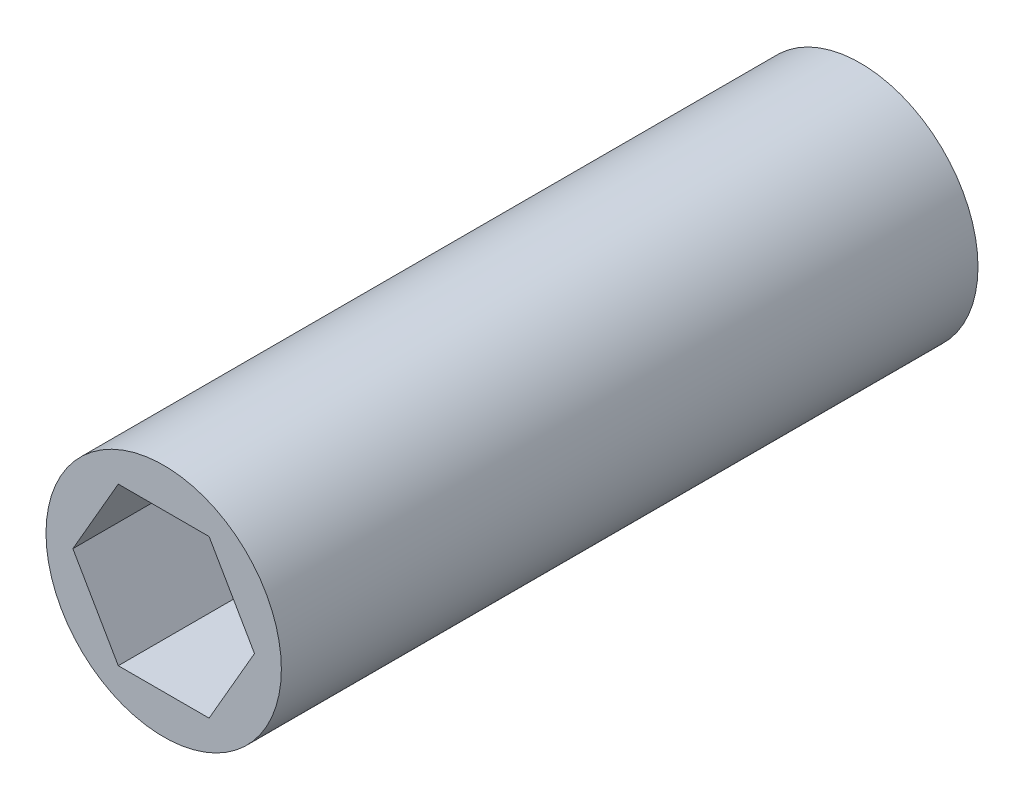
SolidWorks part; units mm, degrees
ref_plane "Front Plane" through (0, 0, 0) normal (0, 0, 1) x (1, 0, 0)
ref_plane "Top Plane" through (0, 0, 0) normal (0, 1, 0) x (1, 0, 0)
ref_plane "Right Plane" through (0, 0, 0) normal (1, 0, 0) x (0, 0, -1)
sketch "Sketch1" plane through (0, 0, 0) normal (0, 0, 1) x (1, 0, 0)
  line L1 (5.7879, 0) -> (2.894, 5.0125)
  line L2 (2.894, 5.0125) -> (-2.894, 5.0125)
  line L3 (-2.894, 5.0125) -> (-5.7879, 0)
  line L4 (-5.7879, 0) -> (-2.894, -5.0125)
  line L5 (-2.894, -5.0125) -> (2.894, -5.0125)
  line L6 (2.894, -5.0125) -> (5.7879, 0)
  circle A0 centre (0, 0) radius 7.5
  circle A1 centre (0, 0) radius 5.0125 construction
  dimension "D1" = 10.025
  dimension "D2" = 15
extrude "Boss-Extrude1" add sketch "Sketch1" along normal mid plane 44.4
ref_axis "Axis1" through (0, 0, 23.4358) along (0, 0, -1)
